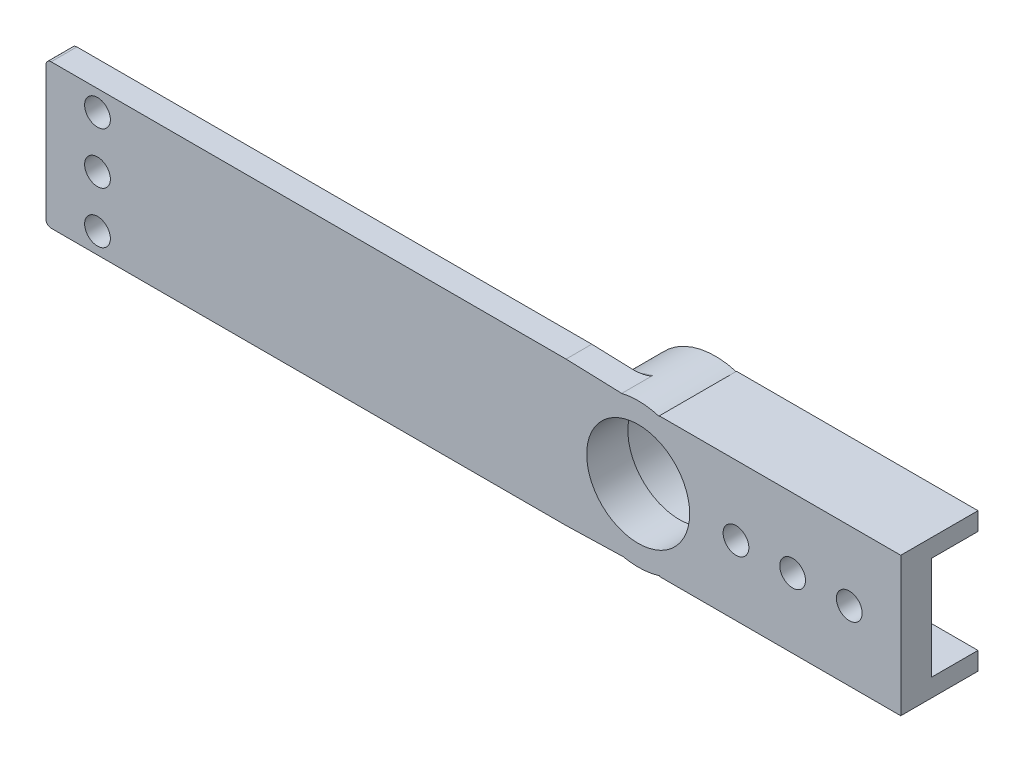
SolidWorks part; units mm, degrees
ref_plane "前视基准面" through (0, 0, 0) normal (0, 0, 1) x (1, 0, 0)
ref_plane "上视基准面" through (0, 0, 0) normal (0, 1, 0) x (1, 0, 0)
ref_plane "右视基准面" through (0, 0, 0) normal (1, 0, 0) x (0, 0, -1)
sketch "草图1" plane through (0, 0, 0) normal (0, 0, 1) x (1, 0, 0)
  line L1 (20, -10) -> (-20, -10)
  line L2 (20, -10) -> (20, 10)
  line L3 (20, 10) -> (-20, 10)
  line L4 (-20, -10) -> (-20, 10)
  line L5 (20, -10) -> (-20, 10) construction
  line L6 (20, 10) -> (-20, -10) construction
  point P0 (0, 0)
  dimension "D1" = 40
  dimension "D2" = 20
extrude "凸台-拉伸1" add sketch "草图1" along normal blind 6
sketch "草图2" plane through (0, 0, 6) normal (0, 0, 1) x (1, 0, 0)
  line L0 (20, -10) -> (20, 10) construction
  circle A0 centre (10, 0) radius 2.5
  circle A1 centre (-1, 0) radius 2.5
  circle A2 centre (-12, 0) radius 2.5
  dimension "D1" = 10
  dimension "D2" = 5
  dimension "D3" = 3
extrude "切除-拉伸1" cut sketch "草图2" against normal through all
sketch "草图3" plane through (0, 0, 6) normal (0, 0, 1) x (1, 0, 0)
  line L0 (20, 13.5) -> (20, 10)
  line L1 (20, -13.5) -> (-26.894, -13.5)
  line L3 (20, 13.5) -> (-26.894, 13.5)
  line L4 (-20, 10) -> (-20, -10)
  line L5 (-20, -10) -> (20, -10)
  line L6 (20, -10) -> (20, 10)
  line L7 (20, 10) -> (-20, 10)
  line L8 (-20, 10) -> (-20, -10)
  line L9 (-20, -10) -> (20, -10)
  line L10 (20, -10) -> (20, 10)
  line L11 (20, 10) -> (-20, 10)
  line L12 (-26.894, -13.5) -> (-26.894, 13.5)
  line L13 (20, -10.0394) -> (-26.894, 13.5) construction
  line L14 (20, 10.0394) -> (-26.894, -13.5) construction
  line L15 (20, -10) -> (20, -13.5)
  circle A0 centre (-31, 0) radius 11
  circle A1 centre (-31, 0) radius 14
  point P2 (0, 0)
  line M10 (-20, 10) -> (-20, -10)
  line M11 (-20, -10) -> (20, -10)
  line M13 (20, 10) -> (-20, 10)
  dimension "D3" = 22
  dimension "D4" = 28
  dimension "D2" = 3.5
  dimension "D1" = 0
extrude "凸台-拉伸2" add sketch "草图3" against normal blind 15 contours L3 A1 L1 L12 A0 | A1 L1 L15 M11 M10 | L1 A1 L8 A0 L12 | L8 A1 L3 L12 A0 | L8 A1 | A1 L0 L3 M10 M13 region at (-1.9449, 11.7771, 6) region at (-1.9449, -11.7771, 6) region at (-23.0173, 9.0328, 6) region at (-27.2274, 11.7946, 6) region at (-18.7882, 0, 6) region at (-23.0173, -9.0328, 6)
sketch "草图5" plane through (0, 0, 6) normal (0, 0, 1) x (1, 0, 0)
  circle A0 centre (-31, 0) radius 10
  circle A1 centre (-31, 0) radius 11 construction
  circle A2 centre (-31, 0) radius 11
  dimension "D1" = 20
extrude "凸台-拉伸3" add sketch "草图5" against normal blind 8
sketch "草图6" plane through (0, 0, 6) normal (0, 0, 1) x (1, 0, 0)
  circle A0 centre (-31, 0) radius 8.5
  circle A1 centre (-31, 0) radius 10 construction
  circle A2 centre (-31, 0) radius 10
  dimension "D1" = 17
sketch "草图8" plane through (0, 0, 6) normal (0, 0, 1) x (1, 0, 0)
  line L0 (20, -13.5) -> (20, 13.5) construction
  line L1 (20, -13.5) -> (-26.894, -13.5) construction
  line L2 (20, 13.5) -> (-26.894, 13.5) construction
  line L3 (20, -13.5) -> (20, 13.5)
  line L4 (20, -13.5) -> (-26.894, -13.5)
  line L5 (20, 13.5) -> (-26.894, 13.5)
  line L6 (-45, -14) -> (-26.894, -13.5)
  line L7 (-45, -14) -> (-146, -14)
  line L8 (-45, -14) -> (-45, 14)
  line L9 (-45, 14) -> (-146, 14)
  line L10 (-146, -14) -> (-146, 14)
  line L11 (-45, -14) -> (-146, 14) construction
  line L12 (-45, 14) -> (-146, -14) construction
  line L13 (-45, 14) -> (-26.894, 13.3843)
  line L14 (-12, 0) -> (-31, 0)
  arc A0 (-26.894, 13.3843) -> (-26.894, -13.3843) centre (-31, 0) ccw construction
  arc A1 (-26.894, 13.3843) -> (-26.894, -13.3843) centre (-31, 0) ccw
  point P6 (-95.5, 0)
  arc M11 (-26.894, 13.3843) -> (-26.894, -13.3843) centre (-31, 0) ccw
  dimension "D1" = 28
  dimension "D2" = 101
  dimension "D3" = 14
extrude "凸台-拉伸4" add sketch "草图8" against normal blind 5 contours L10 L7 L8 L9 | L8 L6 M11 | L13 L8 M11 region at (-42.1177, -10.7223, 6) region at (-95.5, 0, 6) region at (-42.1603, 10.6928, 6)
fillet "圆角1" radius 1 1 edges at (-44.9993, -0.1411, 1)
fillet "圆角2" radius 1 2 edges at (-146, 14, 3.5) (-146, -14, 3.5)
sketch "草图9" plane through (0, 0, 6) normal (0, 0, 1) x (1, 0, 0)
  line L0 (-146, 0) -> (-136, 0) construction
  line L1 (-146, -13) -> (-146, 13) construction
  circle A0 centre (-136, 0) radius 2.5
  circle A1 centre (-136, 10) radius 2.5
  circle A2 centre (-136, -10) radius 2.5
  dimension "D2" = 2
  dimension "5" = 5
  dimension "D1" = 10
  dimension "D3" = 2
extrude "切除-拉伸2" cut sketch "草图9" against normal blind 5
